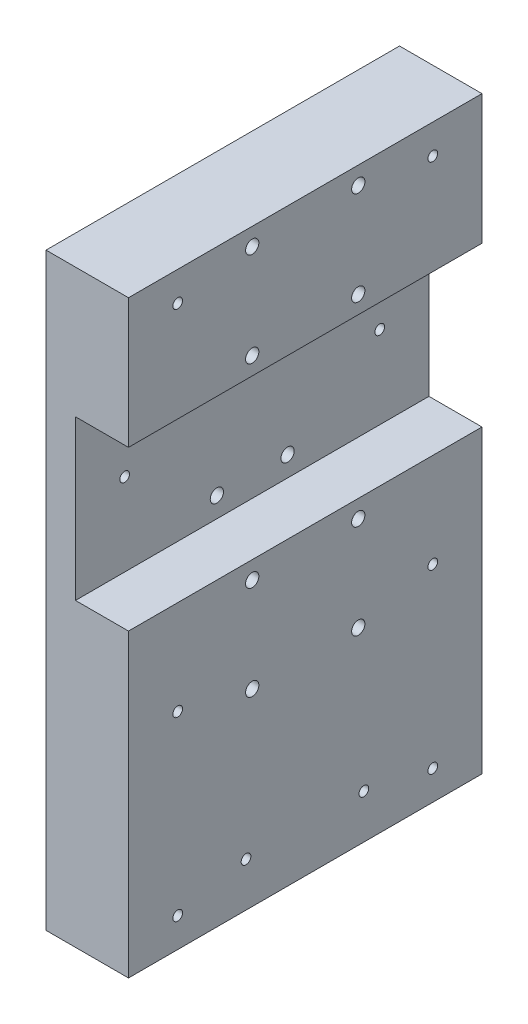
SolidWorks part; units mm, degrees
ref_plane "Front Plane" through (0, 0, 0) normal (0, 0, 1) x (1, 0, 0)
ref_plane "Top Plane" through (0, 0, 0) normal (0, 1, 0) x (1, 0, 0)
ref_plane "Right Plane" through (0, 0, 0) normal (1, 0, 0) x (0, 0, -1)
sketch "Sketch1" plane through (0, 0, 0) normal (0, 0, 1) x (1, 0, 0)
  line L0 (0, 0) -> (0, 200)
  line L1 (0, 200) -> (28, 200)
  line L2 (28, 200) -> (28, 156)
  line L3 (10, 156) -> (10, 102)
  line L4 (10, 156) -> (28, 156)
  line L5 (10, 102) -> (28, 102)
  line L6 (28, 102) -> (28, 0)
  line L7 (28, 0) -> (0, 0)
  line L8 (-49.525, 129) -> (95.9642, 129) construction
  point P12 (10, 129)
  dimension "D1" = 200
  dimension "D2" = 27
  dimension "D3" = 18
  dimension "D4" = 28
  dimension "D6" = 71
extrude "Boss-Extrude1" add sketch "Sketch1" along normal blind 120 contours L0 L1 L2 L4 L3 L5 L6 L7
sketch "Sketch2" plane through (0, 0, 0) normal (-1, 0, 0) x (0, 0, 1)
  line L0 (60, 200) -> (60, 0) construction
  line L1 (120, 200) -> (0, 200) construction
  line L2 (120, 0) -> (0, 0) construction
  point P6 (78, 194)
  point P7 (78, 162)
  point P8 (72, 148.86)
  point P9 (72, 108.86)
  point P10 (78, 96)
  point P11 (78, 64)
  point P12 (42, 64)
  point P13 (42, 96)
  point P14 (48, 108.86)
  point P15 (48, 148.86)
  point P16 (42, 162)
  point P17 (42, 194)
  dimension "D1" = 6
  dimension "D2" = 32
  dimension "D3" = 45.14
  dimension "D4" = 40
  dimension "D5" = 98
  dimension "D6" = 32
  dimension "D7" = 18
  dimension "D8" = 12
  dimension "D9" = 18
hole_wizard "CBORE for M4 SHCS4" positions "3DSketch2" profile "Sketch4" counterbore size "M4" standard "ANSI Metric" end condition through all
sketch3d "3DSketch2"
  point P0 (0, 194, 78)
  point P3 (0, 162, 78)
  point P6 (0, 148.86, 72)
  point P9 (0, 108.86, 72)
  point P12 (0, 96, 78)
  point P15 (0, 64, 78)
  point P18 (0, 64, 42)
  point P21 (0, 96, 42)
  point P24 (0, 108.86, 48)
  point P27 (0, 148.86, 48)
  point P30 (0, 162, 42)
  point P33 (0, 194, 42)
sketch "Sketch4" plane through (0, 194, 78) normal (0, 1, 0) x (0, 0, 1)
  line L0 (0, 0) -> (0, 28)
  line L1 (0, 28) -> (2.25, 28)
  line L3 (2.25, 28) -> (2.25, 4)
  line L4 (2.25, 4) -> (4, 4)
  line L5 (4, 4) -> (4, 0)
  line L7 (4, 0) -> (0, 0)
  line L11 (0, -6.35) -> (0, 107.95) construction
  dimension "Thru Hole Dia." = 4.5
  dimension "Thru Hole Depth" = 28
  dimension "C'Bore Dia." = 8
  dimension "C'Bore Depth" = 4
sketch "Sketch5" plane through (0, 0, 0) normal (-1, 0, 0) x (0, 0, 1)
  line L0 (16.7, 200) -> (16.7, 0) construction
  line L1 (120, 200) -> (0, 200) construction
  line L2 (120, 0) -> (0, 0) construction
  line L3 (60, 200) -> (60, 0) construction
  line L4 (60, 200) -> (60, 0) construction
  line L5 (103.3, 200) -> (103.3, 0) construction
  point P12 (16.7, 190)
  point P13 (103.3, 10)
  point P14 (16.7, 130)
  point P15 (16.7, 70)
  point P16 (16.7, 10)
  point P17 (103.3, 70)
  point P18 (103.3, 130)
  point P19 (103.3, 190)
  dimension "D1" = 43.3
  dimension "D2" = 10
  dimension "D3" = 4
hole_wizard "M4 Tapped Hole1" positions "3DSketch3" profile "Sketch6" tap size "M4" standard "ISO" end condition through all
sketch3d "3DSketch3"
  point P0 (0, 190, 16.7)
  point P3 (0, 130, 16.7)
  point P6 (0, 70, 16.7)
  point P9 (0, 10, 16.7)
  point P12 (0, 10, 103.3)
  point P15 (0, 70, 103.3)
  point P18 (0, 130, 103.3)
  point P21 (0, 190, 103.3)
sketch "Sketch6" plane through (0, 190, 16.7) normal (0, 1, 0) x (0, 0, 1)
  line L0 (0, 0) -> (0, 28)
  line L1 (0, 28) -> (1.65, 28)
  line L2 (1.65, 28) -> (1.65, 0)
  line L5 (1.65, 0) -> (0, 0)
  line L11 (0, -6.35) -> (0, 107.95) construction
  dimension "Thread Major Dia." = 3.3
  dimension "Thru Tap Drill Depth" = 28
ref_plane "Plane1" through (0, 0, 60) normal (0, 0, -1) x (-1, 0, 0)
sketch "Sketch7" plane through (0, 0, 0) normal (0, -1, 0) x (1, 0, 0)
  line L0 (14, 120) -> (14, 0) construction
  line L1 (28, 120) -> (0, 120) construction
  line L2 (28, 0) -> (0, 0) construction
  line L3 (28, 60) -> (0, 60) construction
  line L4 (28, 120) -> (28, 0) construction
  line L5 (0, 120) -> (0, 0) construction
  point P12 (14, 60)
  point P13 (14, 95)
  point P14 (14, 25)
  dimension "D1" = 35
hole_wizard "M8 Tapped Hole1" positions "3DSketch4" profile "Sketch8" tap size "M8" standard "ISO"
sketch3d "3DSketch4"
  point P0 (14, 0, 95)
  point P3 (14, 0, 60)
  point P6 (14, 0, 25)
sketch "Sketch8" plane through (14, 0, 95) normal (1, 0, 0) x (0, 0, -1)
  line L0 (0, 0) -> (0, 17.7929)
  line L1 (0, 17.7929) -> (3.4, 15.75)
  line L2 (3.4, 15.75) -> (3.4, 0)
  line L5 (3.4, 0) -> (0, 0)
  line L10 (0, 17.7929) -> (-3.4, 15.75) construction
  line L11 (0, -6.35) -> (0, 107.95) construction
  dimension "Tap Drill Dia." = 6.8
  dimension "Tap Drill Depth" = 15.75
  dimension "Drill Angle" = 118
sketch "Sketch9" plane through (28, 0, 0) normal (1, 0, 0) x (0, 0, -1)
  line L0 (-40.1, 23.78) -> (-40.1, 0) construction
  line L1 (-80.1, 23.78) -> (-80.1, 0) construction
  line L8 (-120, 0) -> (0, 0) construction
  line L11 (-120, 0) -> (0, 0) construction
  point P8 (-40.1, 15)
  point P9 (-80.1, 15)
  dimension "D1" = 15
hole_wizard "M4 Tapped Hole2" positions "3DSketch5" profile "Sketch10" tap size "M4" standard "ISO" end condition through all
sketch3d "3DSketch5"
  point P0 (28, 15, 80.1)
  point P3 (28, 15, 40.1)
sketch "Sketch10" plane through (28, 15, 80.1) normal (0, 1, 0) x (0, 0, -1)
  line L0 (0, 0) -> (0, 28)
  line L1 (0, 28) -> (1.65, 28)
  line L2 (1.65, 28) -> (1.65, 0)
  line L5 (1.65, 0) -> (0, 0)
  line L11 (0, -6.35) -> (0, 107.95) construction
  dimension "Thread Major Dia." = 3.3
  dimension "Thru Tap Drill Depth" = 28
